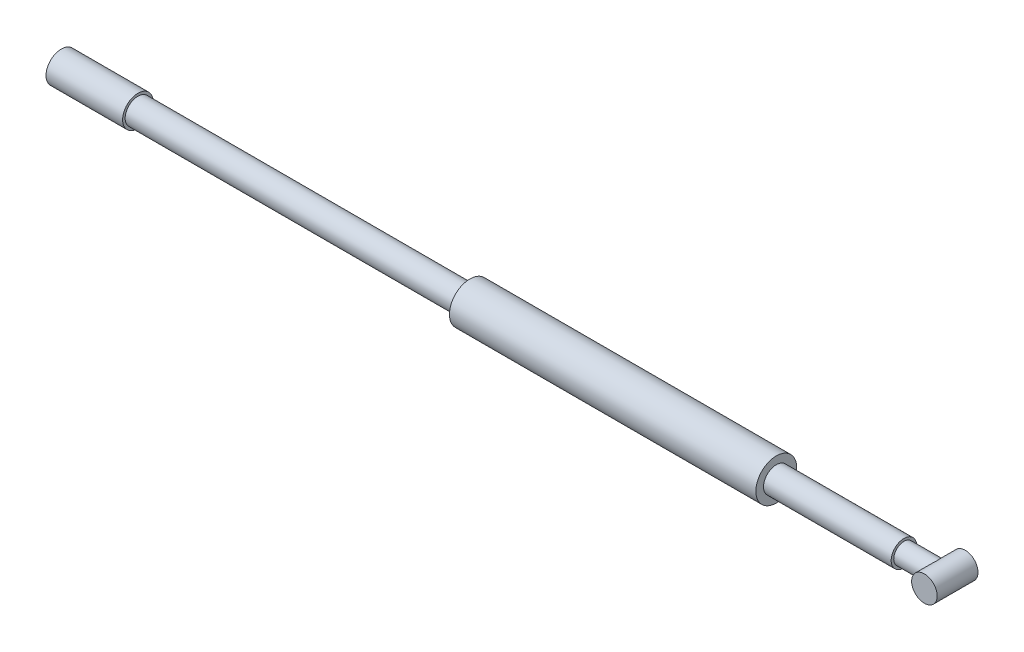
SolidWorks part; units mm, degrees
ref_plane "Front Plane" through (0, 0, 0) normal (0, 0, 1) x (1, 0, 0)
ref_plane "Top Plane" through (0, 0, 0) normal (0, 1, 0) x (1, 0, 0)
ref_plane "Right Plane" through (0, 0, 0) normal (1, 0, 0) x (0, 0, -1)
sketch "Sketch1" plane through (0, 0, 0) normal (1, 0, 0) x (0, 0, -1)
  circle A0 centre (0, 0) radius 2.5
  dimension "D1" = 5
extrude "Boss-Extrude1" add sketch "Sketch1" along normal blind 150
sketch "Sketch3" plane through (0, 0, 0) normal (-1, 0, 0) x (0, 0, 1)
  circle A0 centre (0, 0) radius 3
  dimension "D1" = 6
extrude "Boss-Extrude2" add sketch "Sketch3" along normal blind 15
sketch "Sketch4" plane through (150, 0, 0) normal (1, 0, 0) x (0, 0, -1)
  circle A0 centre (0, 0) radius 2
  dimension "D1" = 4
extrude "Boss-Extrude3" add sketch "Sketch4" along normal blind 8
sketch "Sketch5" plane through (0, 0, 0) normal (0, 0, 1) x (1, 0, 0)
  line L0 (158, -2) -> (158, 2) construction
  circle A0 centre (158, 0) radius 2.5
  dimension "D1" = 5
extrude "Boss-Extrude4" add sketch "Sketch5" along normal blind 4 and the other way blind 4
sketch3d "3DSketch1"
  circle A0 centre (65, 0, 0) radius 4
  point P2 (61, 0, 0)
  dimension "D2" = 8
  dimension "D1" = 80
extrude "Boss-Extrude5" add sketch "3DSketch1" along direction (1, 0, 0) on the side of the normal blind 60
sketch3d "3DSketch4"
  line L0 (0, 2.5, 0) -> (65, 2.5, 0) construction
  circle A0 centre (0, 0, 0) radius 2.5 construction
  circle A1 centre (65, 0, 0) radius 2.5 construction
  point P4 (-2.5, 0, 0)
  point P7 (67.5, 0, 0)
  dimension "D1" = 2.5
